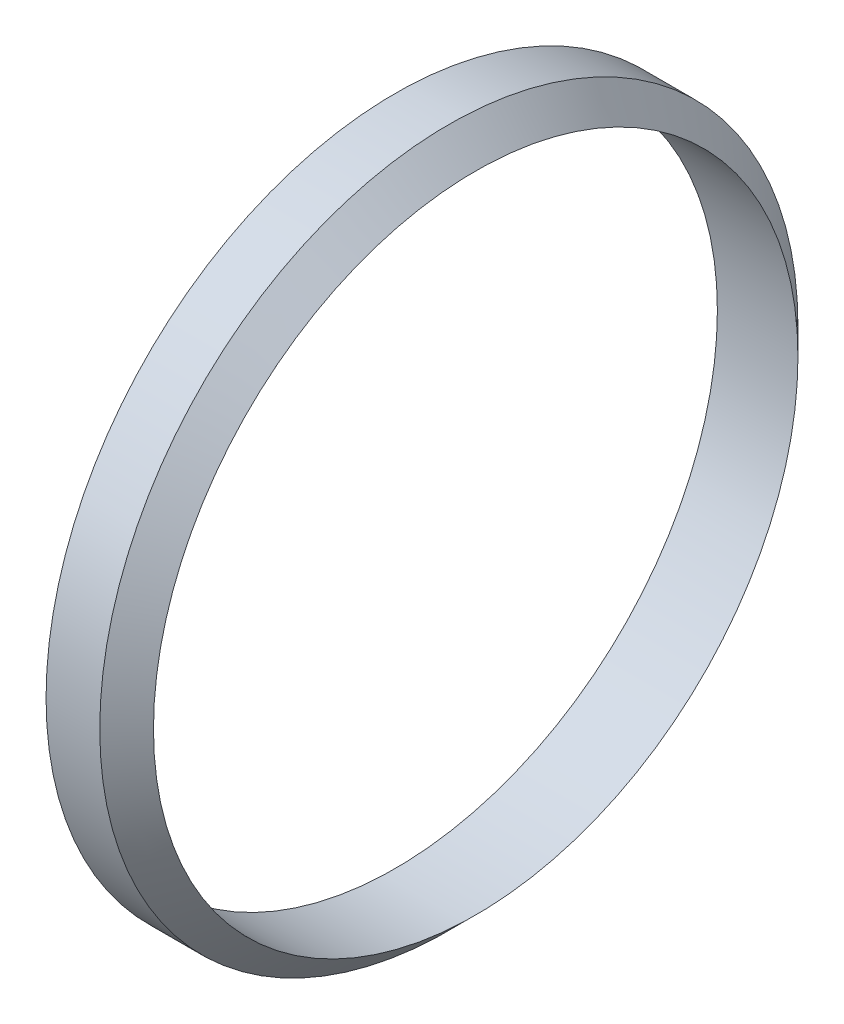
SolidWorks part; units mm, degrees
ref_plane "Front Plane" through (0, 0, 0) normal (0, 0, 1) x (1, 0, 0)
ref_plane "Top Plane" through (0, 0, 0) normal (0, 1, 0) x (1, 0, 0)
ref_plane "Right Plane" through (0, 0, 0) normal (1, 0, 0) x (0, 0, -1)
sketch "Sketch1" plane through (0, 0, 0) normal (1, 0, 0) x (0, 0, -1)
  circle A0 centre (0, 0) radius 13
  circle A1 centre (0, 0) radius 12
  dimension "D1" = 26
  dimension "D2" = 24
extrude "Boss-Extrude1" add sketch "Sketch1" along normal blind 3
chamfer "Chamfer1" distance 1 angle 45 1 edges at (3, 0, -13)
